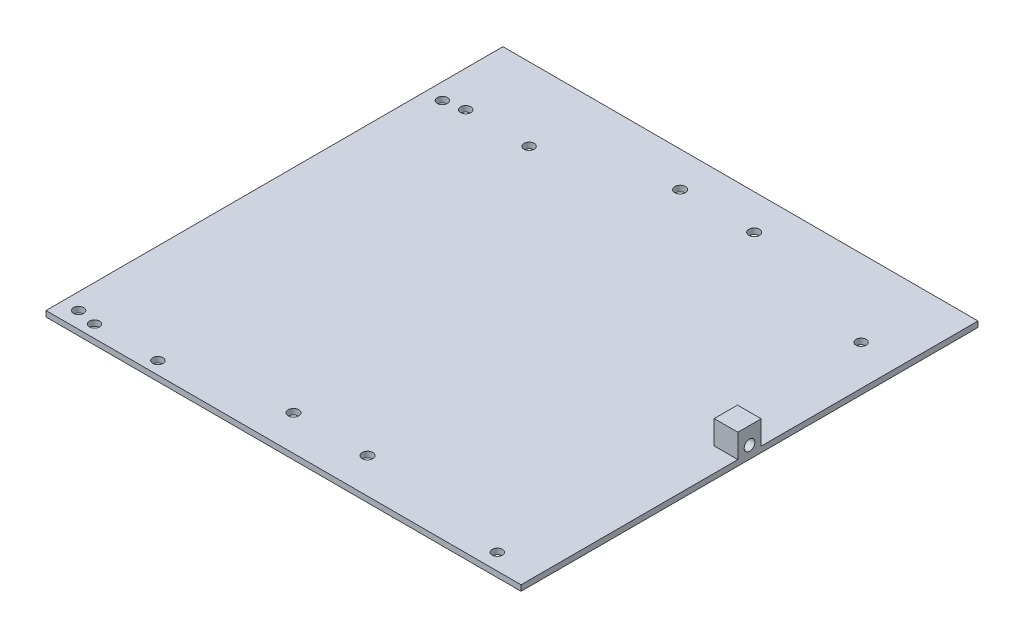
SolidWorks part; units mm, degrees
material "Thornel Mat VMA"
ref_plane "Front Plane" through (0, 0, 0) normal (0, 0, 1) x (1, 0, 0)
ref_plane "Top Plane" through (0, 0, 0) normal (0, 1, 0) x (1, 0, 0)
ref_plane "Right Plane" through (0, 0, 0) normal (1, 0, 0) x (0, 0, -1)
sketch "Sketch1" plane through (0, 0, 0) normal (0, 1, 0) x (1, 0, 0)
  line L1 (0, 0) -> (101.88, 0)
  line L2 (0, 0) -> (0, -98)
  line L3 (0, -98) -> (101.88, -98)
  line L4 (101.88, 0) -> (101.88, -98)
  dimension "D1" = 98
  dimension "D2" = 101.88
extrude "Boss-Extrude1" add sketch "Sketch1" along normal blind 1.2192
sketch "Sketch5" plane through (0, 0, 0) normal (0, -1, 0) x (-1, 0, 0)
  line L1 (0, -98) -> (-101.88, -98) construction
  line L2 (0, 0) -> (0, -98) construction
  line L3 (-101.88, 0) -> (0, 0) construction
  circle A0 centre (-3.5, -94.5) radius 1.0922
  circle A1 centre (-7.7, -95.3) radius 1.0922
  circle A2 centre (-21.3, -95.3) radius 1.0922
  circle A3 centre (-93.3, -94.5) radius 1.0922
  circle A4 centre (-93.3, -16.5) radius 1.0922
  circle A5 centre (-3.5, -16.5) radius 1.0922
  circle A6 centre (-7.7, -15.7) radius 1.0922
  circle A7 centre (-21.3, -15.7) radius 1.0922
  dimension "D1" = 3.5
  dimension "D2" = 93.3
  dimension "D3" = 72
  dimension "D5" = 85.6
  dimension "D6" = 2.7
  dimension "D7" = 89.8
  dimension "D8" = 3.5
  dimension "D9" = 16.5
  dimension "D10" = 93.3
  dimension "D11" = 72
  dimension "D12" = 2.1844
  dimension "D13" = 15.7
  dimension "D15" = 15.7
  dimension "D16" = 16.5
  dimension "D17" = 89.8
  dimension "D4" = 2.7
  dimension "D14" = 85.6
extrude "Cut-Extrude1" cut sketch "Sketch5" against normal up to next
sketch "Sketch6" plane through (0, 1.2192, 0) normal (0, 1, 0) x (1, 0, 0)
  line L0 (101.88, 0) -> (0, 0) construction
  line L1 (61.4175, -7.5406) -> (45.5425, -7.5406) construction
  line L3 (101.88, -49) -> (0, -49) construction
  line L4 (101.88, -98) -> (101.88, 0) construction
  line L5 (0, 0) -> (0, -98) construction
  circle A0 centre (61.4175, -7.5406) radius 1.143
  circle A1 centre (45.5425, -7.5406) radius 1.143
  circle A2 centre (45.5425, -90.4594) radius 1.143
  circle A3 centre (61.4175, -90.4594) radius 1.143
  dimension "D1" = 2.286
  dimension "D2" = 2.286
  dimension "D6" = 40.4625
  dimension "D3" = 7.5406
  dimension "D4" = 7.5406
  dimension "D5" = 15.875
extrude "Cut-Extrude2" cut sketch "Sketch6" against normal up to next
sketch "Sketch10" plane through (101.88, 0, 0) normal (1, 0, 0) x (0, 0, -1)
  line L0 (-98, 1.2192) -> (0, 1.2192) construction
  line L1 (-46.5, 1.2192) -> (-51.5, 1.2192)
  line L2 (-46.5, 1.2192) -> (-46.5, 6.2992)
  line L3 (-46.5, 6.2992) -> (-51.5, 6.2992)
  line L4 (-51.5, 1.2192) -> (-51.5, 6.2992)
  line L5 (-98, 0.6096) -> (0, 0.6096) construction
  line L6 (-98, 1.2192) -> (-98, 0) construction
  line L7 (0, 1.2192) -> (0, 0) construction
  circle A0 centre (-49, 2.648) radius 1.143
  point P6 (-49, 1.2192)
  point P7 (-49, 1.2192)
  point P9 (-49, 6.2992)
  dimension "D3" = 2.286
  dimension "D4" = 2.0383
  dimension "D1" = 5.08
  dimension "D2" = 5
extrude "Boss-Extrude2" add sketch "Sketch10" against normal blind 5.08
